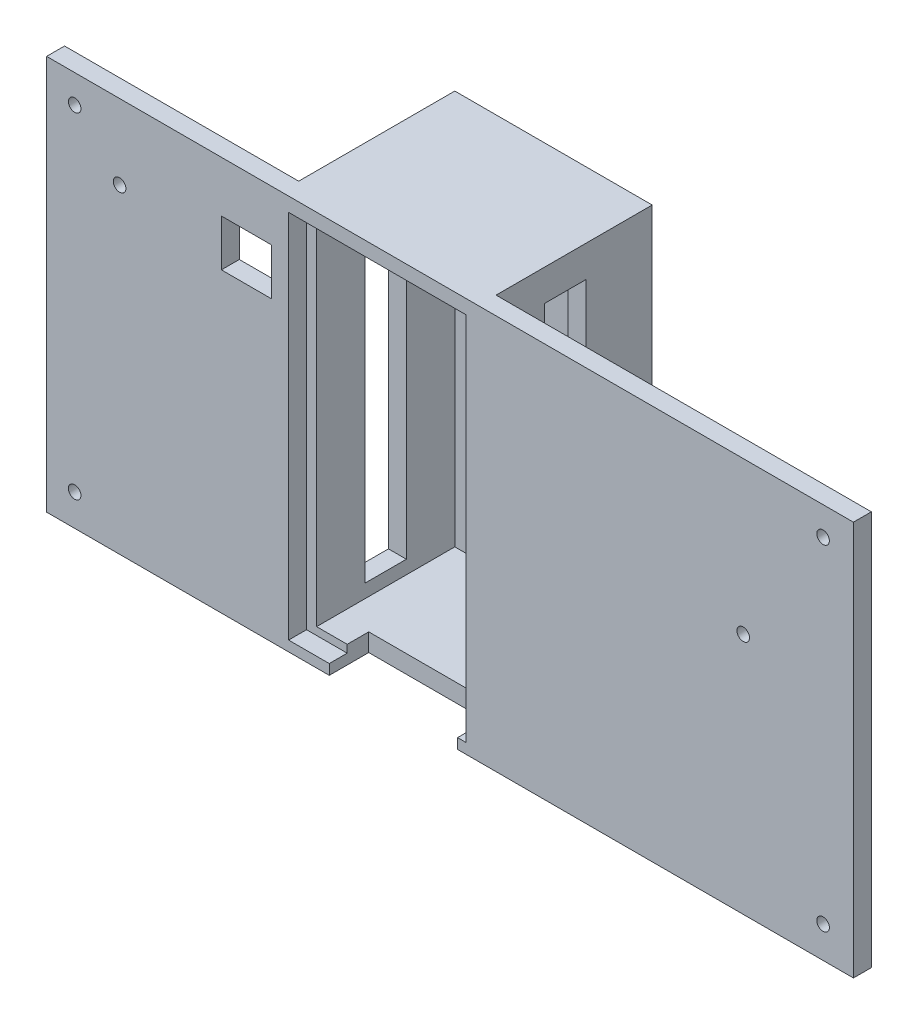
SolidWorks part; units mm, degrees
ref_plane "Front Plane" through (0, 0, 0) normal (0, 0, 1) x (1, 0, 0)
ref_plane "Top Plane" through (0, 0, 0) normal (0, 1, 0) x (1, 0, 0)
ref_plane "Right Plane" through (0, 0, 0) normal (1, 0, 0) x (0, 0, -1)
sketch "Sketch1" plane through (0, 0, 0) normal (0, 0, 1) x (1, 0, 0)
  line L1 (3057.4972, 13550.2491) -> (2943.2926, 13550.2491)
  line L2 (3057.4972, 13550.2491) -> (3057.4972, 13494.3691)
  line L3 (3057.4972, 13494.3691) -> (2943.2926, 13494.3691)
  line L4 (2943.2926, 13550.2491) -> (2943.2926, 13494.3691)
extrude "Boss-Extrude1" add sketch "Sketch1" against normal blind 2.54
sketch "Sketch2" plane through (0, 0, -2.54) normal (0, 0, -1) x (-1, 0, 0)
  line L1 (-2975.1428, 13543.0496) -> (-2968.0308, 13543.0496)
  line L2 (-2975.1428, 13543.0496) -> (-2975.1428, 13536.4456)
  line L3 (-2975.1428, 13536.4456) -> (-2968.0308, 13536.4456)
  line L4 (-2968.0308, 13543.0496) -> (-2968.0308, 13536.4456)
  line L5 (-2975.1428, 13543.0496) -> (-2968.0308, 13536.4456) construction
  line L6 (-2975.1428, 13536.4456) -> (-2968.0308, 13543.0496) construction
  point P0 (-2971.5868, 13539.7476)
  dimension "D1" = 6.604
  dimension "D2" = 7.112
extrude "Cut-Extrude2" cut sketch "Sketch2" against normal up to next contours L4 L1 L2 L3 region at (2971.5868, 13539.7476, -2.54)
sketch "Sketch5" plane through (0, 0, -2.54) normal (0, 0, -1) x (-1, 0, 0)
  line L1 (-3004.372, 13550.2491) -> (-2976.432, 13550.2491)
  line L2 (-3004.372, 13550.2491) -> (-3004.372, 13494.3691)
  line L3 (-3004.372, 13494.3691) -> (-2976.432, 13494.3691)
  line L4 (-2976.432, 13550.2491) -> (-2976.432, 13494.3691)
  dimension "D1" = 27.94
extrude "Boss-Extrude2" add sketch "Sketch5" along normal blind 19.558
shell "Shell2" thickness 2.54 removed face at (2990.402, 13522.3091, -22.098)
sketch "Sketch6" plane through (0, 0, -2.54) normal (0, 0, -1) x (-1, 0, 0)
  line L1 (-3002.6439, 13548.2543) -> (-2977.5469, 13548.2543)
  line L2 (-3002.6439, 13548.2543) -> (-3002.6439, 13495.8195)
  line L3 (-3002.6439, 13495.8195) -> (-2977.5469, 13495.8195)
  line L4 (-2977.5469, 13548.2543) -> (-2977.5469, 13495.8195)
extrude "Cut-Extrude3" cut sketch "Sketch6" against normal through all
sketch "Sketch7" plane through (3004.372, 0, 0) normal (1, 0, 0) x (0, 0, -1)
  line L0 (22.098, 13522.3091) -> (2.54, 13522.3091) construction
  line L1 (22.098, 13550.2491) -> (22.098, 13494.3691) construction
  line L2 (2.54, 13494.3691) -> (2.54, 13550.2491) construction
  line L4 (9.393, 13545.7974) -> (15.245, 13545.7974)
  line L5 (9.393, 13545.7974) -> (9.393, 13498.8208)
  line L6 (9.393, 13498.8208) -> (15.245, 13498.8208)
  line L7 (15.245, 13545.7974) -> (15.245, 13498.8208)
  line L8 (9.393, 13545.7974) -> (15.245, 13498.8208) construction
  line L9 (9.393, 13498.8208) -> (15.245, 13545.7974) construction
  point P6 (12.319, 13522.3091)
  dimension "D1" = 46.9765
  dimension "D2" = 5.852
extrude "Cut-Extrude4" cut sketch "Sketch7" against normal through all
sketch "Sketch8" plane through (0, 13494.3691, 0) normal (0, -1, 0) x (1, 0, 0)
  line L3 (3001.4606, 0) -> (2983.2996, 0)
  line L5 (3001.4606, -5.588) -> (2983.2996, -5.588)
  line L7 (3001.4606, -22.098) -> (3001.4606, 0) construction
  line L8 (3004.372, -22.098) -> (2976.432, -22.098) construction
  line L9 (2983.2996, -22.098) -> (2983.2996, 0) construction
  line L10 (3001.4606, 0) -> (3001.4606, -5.588)
  line L11 (2983.2996, 0) -> (2983.2996, -5.588)
  dimension "D1" = 18.161
extrude "Cut-Extrude5" cut sketch "Sketch8" against normal blind 19.558
hole_wizard "CBORE for #0 Binding Head Machine Screw1" positions "Sketch10" profile "Sketch9" counterbore size "#0" standard "ANSI Inch" end condition through all
sketch "Sketch10" plane through (0, 0, -2.54) normal (0, 0, -1) x (-1, 0, 0)
  point P0 (-3041.897, 13528.711)
  point P1 (-2953.6183, 13539.6492)
sketch "Sketch9" plane through (3041.897, 13528.711, -2.54) normal (1, 0, 0) x (0, 1, 0)
  line L0 (0, 0) -> (0, 2.54)
  line L1 (0, 2.54) -> (0.889, 2.54)
  line L3 (0.889, 2.54) -> (0.889, 0.8128)
  line L4 (1.985, 0.8128) -> (0.889, 0.8128)
  line L5 (1.985, 0.8128) -> (1.985, 0.635)
  line L6 (1.985, 0.635) -> (2.62, 0)
  line L7 (2.62, 0) -> (0, 0)
  line L8 (-1.985, 0.635) -> (-2.62, 0) construction
  line L11 (0, -6.35) -> (0, 107.95) construction
  dimension "Thru Hole Dia." = 1.778
  dimension "Thru Hole Depth" = 2.54
  dimension "C'Bore Dia." = 3.97
  dimension "C'Bore Depth" = 0.8128
  dimension "Near C'Sink Dia." = 5.24
  dimension "Near C'Sink Angle" = 90
hole_wizard "CBORE for #0 Binding Head Machine Screw2" positions "Sketch15" profile "Sketch14" counterbore size "#0" standard "ANSI Inch" end condition through all
sketch "Sketch15" plane through (0, 0, -2.54) normal (0, 0, -1) x (-1, 0, 0)
  point P0 (-3053.2045, 13546.2565)
  point P2 (-3053.2045, 13498.8311)
  point P4 (-2925.5288, 13498.7881)
  point P6 (-2947.2615, 13498.8311)
  point P8 (-2947.2615, 13546.2565)
sketch "Sketch14" plane through (3053.2045, 13546.2565, -2.54) normal (1, 0, 0) x (0, 1, 0)
  line L0 (0, 0) -> (0, 2.54)
  line L1 (0, 2.54) -> (0.889, 2.54)
  line L3 (0.889, 2.54) -> (0.889, 0.8128)
  line L4 (1.985, 0.8128) -> (0.889, 0.8128)
  line L5 (1.985, 0.8128) -> (1.985, 0.635)
  line L6 (1.985, 0.635) -> (2.62, 0)
  line L7 (2.62, 0) -> (0, 0)
  line L8 (-1.985, 0.635) -> (-2.62, 0) construction
  line L11 (0, -6.35) -> (0, 107.95) construction
  dimension "Thru Hole Dia." = 1.778
  dimension "Thru Hole Depth" = 2.54
  dimension "C'Bore Dia." = 3.97
  dimension "C'Bore Depth" = 0.8128
  dimension "Near C'Sink Dia." = 5.24
  dimension "Near C'Sink Angle" = 90
sketch "Sketch16" plane through (0, 0, -22.098) normal (0, 0, -1) x (-1, 0, 0)
  line L0 (-2976.432, 13494.3691) -> (-2976.432, 13550.2491) construction
  line L1 (-3004.372, 13550.2491) -> (-2976.432, 13550.2491)
  line L2 (-3004.372, 13550.2491) -> (-3004.372, 13494.3691)
  line L3 (-3004.372, 13494.3691) -> (-2976.432, 13494.3691)
  line L4 (-2976.432, 13550.2491) -> (-2976.432, 13494.3691)
extrude "Boss-Extrude3" add sketch "Sketch16" along normal blind 2.54
